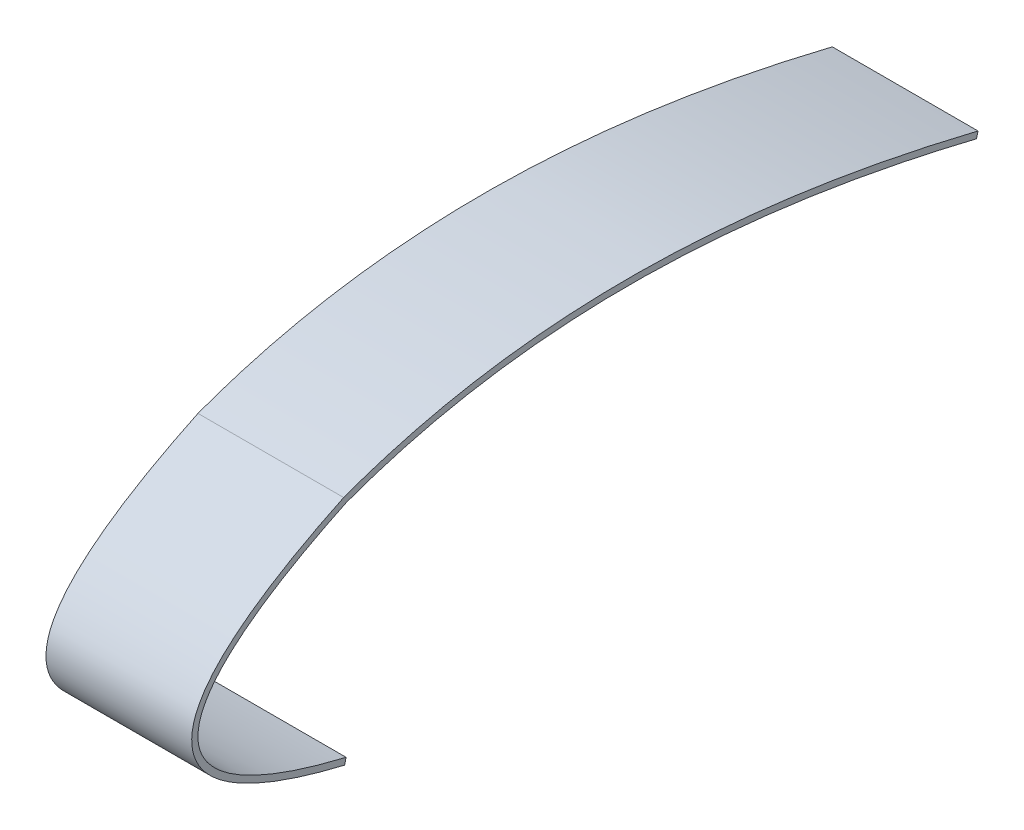
SolidWorks part; units mm, degrees
ref_plane "Front Plane" through (0, 0, 0) normal (0, 0, 1) x (1, 0, 0)
ref_plane "Top Plane" through (0, 0, 0) normal (0, 1, 0) x (1, 0, 0)
ref_plane "Right Plane" through (0, 0, 0) normal (1, 0, 0) x (0, 0, -1)
sketch "Sketch2" plane through (0, 0, 0) normal (1, 0, 0) x (0, 0, -1)
  line L2 (628.1543, 1334.841) -> (635.2765, 1363.9833)
  line L3 (-2400.3471, 275.9245) -> (-2407.3389, 246.7506)
  spline S0 degree 3 poles (628.1543, 1334.841) (-348.2547, 1573.4666) (-1437.4882, 1692.3838) (-2400.3471, 1334.841) knots 0 0 0 0 1 1 1 1
  spline S1 degree 3 poles (-2400.3471, 1334.841) (-2786.9421, 1151.3413) (-3787.594, 608.3949) (-2400.3471, 275.9245) knots 0 0 0 0 1 1 1 1
  spline S2 degree 1 poles (635.2765, 1363.9833) (-2412.0231, 1362.5068) knots 0 0 1 1 construction
  spline S3 degree 1 poles (-2412.0231, 1362.5068) (-2407.3389, 246.7506) knots 0 0 1 1 construction
  spline S4 degree 3 poles (635.2765, 1363.9833) (619.9508, 1367.7287) (589.3108, 1375.1447) (543.1329, 1386.0985) (496.8114, 1396.857) (434.8407, 1410.9365) (357.011, 1428.0151) (263.0692, 1447.6114) (168.6255, 1466.2436) (42.089, 1489.7134) (-117.1194, 1516.311) (-309.4833, 1543.3175) (-567.2573, 1572.0737) (-891.0243, 1593.0977) (-1214.5415, 1590.6869) (-1471.8077, 1572.563) (-1663.6312, 1550.3371) (-1853.974, 1518.9424) (-2011.0611, 1484.6927) (-2135.631, 1452.1725) (-2228.4626, 1425.1554) (-2305.2891, 1400.3961) (-2358.7645, 1381.8577) (-2385.4278, 1372.282) (-2398.7351, 1367.4186) (-2406.341, 1364.6154) (-2410.1282, 1363.2105) (-2412.0231, 1362.5068) knots 0 0 0 0 0.015632 0.031263 0.046895 0.062527 0.09379 0.125053 0.156317 0.18758 0.250107 0.312633 0.37516 0.500213 0.625267 0.687793 0.75032 0.812847 0.875373 0.906637 0.9379 0.969163 0.984795 0.992611 0.996519 0.998473 1.000427 1.000427 1.000427 1.000427
  spline S5 degree 3 poles (-2412.0231, 1362.5068) (-2413.5477, 1361.7832) (-2416.5805, 1360.3431) (-2422.7708, 1357.394) (-2430.6295, 1353.6336) (-2440.2791, 1348.9872) (-2453.4136, 1342.6217) (-2470.3192, 1334.3467) (-2491.3149, 1323.9214) (-2512.9515, 1313.0135) (-2542.5628, 1297.8431) (-2580.8356, 1277.7367) (-2628.2295, 1251.8796) (-2676.5443, 1224.3909) (-2725.236, 1195.3664) (-2789.9379, 1154.7426) (-2869.05, 1100.5803) (-2956.8628, 1030.8175) (-3033.2779, 956.7608) (-3083.8705, 891.5879) (-3114.0846, 837.1887) (-3130.8758, 795.1928) (-3140.9437, 752.0256) (-3143.33, 707.9411) (-3137.1646, 663.5343) (-3121.9196, 619.6013) (-3097.4316, 576.774) (-3063.636, 535.313) (-3020.3329, 495.2029) (-2967.144, 456.3324) (-2903.5684, 418.6021) (-2841.4638, 388.065) (-2786.0113, 364.1744) (-2741.4635, 346.5286) (-2693.8831, 329.1592) (-2643.1963, 312.0718) (-2598.3072, 298.0731) (-2560.7693, 287.0227) (-2531.7934, 278.8102) (-2501.9859, 270.6742) (-2476.446, 263.9589) (-2455.5888, 258.6261) (-2439.7335, 254.6466) (-2426.3381, 251.3461) (-2415.5222, 248.7179) (-2410.0631, 247.4035) (-2407.3389, 246.7506) knots -0.001024 -0.001024 -0.001024 -0.001024 0.002886 0.006796 0.014617 0.022437 0.030258 0.045899 0.06154 0.077181 0.092822 0.124104 0.155386 0.186668 0.21795 0.249232 0.311796 0.37436 0.436924 0.499488 0.53077 0.562052 0.593334 0.624616 0.655898 0.68718 0.718462 0.749744 0.781026 0.812308 0.84359 0.874872 0.890513 0.906154 0.921795 0.937436 0.953077 0.960897 0.968718 0.976538 0.984359 0.988269 0.992179 0.99609 0.998045 1 1 1 1
  point P10 (0, 0)
  dimension "D1" = 30
extrude "Boss-Extrude1" add sketch "Sketch2" along normal blind 350 and the other way blind 350
